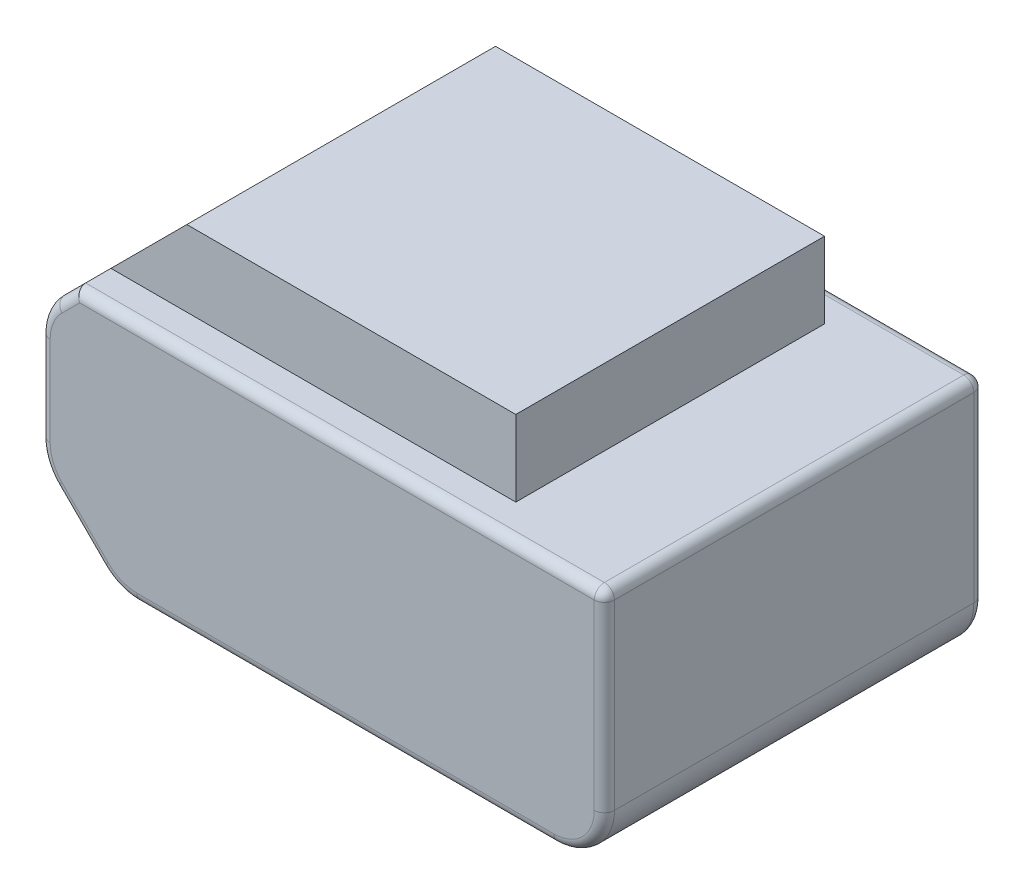
SolidWorks part; units mm, degrees
ref_plane "Front Plane" through (0, 0, 0) normal (0, 0, 1) x (1, 0, 0)
ref_plane "Top Plane" through (0, 0, 0) normal (0, 1, 0) x (1, 0, 0)
ref_plane "Right Plane" through (0, 0, 0) normal (1, 0, 0) x (0, 0, -1)
sketch "Sketch1" plane through (0, 0, 0) normal (0, 1, 0) x (1, 0, 0)
  line L1 (-55.75, 37.5) -> (55.75, 37.5)
  line L2 (-55.75, 37.5) -> (-55.75, -37.5)
  line L3 (-55.75, -37.5) -> (55.75, -37.5)
  line L4 (55.75, 37.5) -> (55.75, -37.5)
  line L5 (-55.75, 37.5) -> (55.75, -37.5) construction
  line L6 (-55.75, -37.5) -> (55.75, 37.5) construction
  point P0 (0, 0)
  dimension "D1" = 75
  dimension "D2" = 111.5
extrude "Boss-Extrude1" add sketch "Sketch1" along normal blind 63
sketch "Sketch2" plane through (0, 0, 37.5) normal (0, 0, 1) x (1, 0, 0)
  line L0 (-55.75, 41) -> (-33.75, 63)
  line L1 (-55.75, 63) -> (-55.75, 0) construction
  line L2 (-55.75, 63) -> (55.75, 63) construction
  line L3 (-55.75, 41) -> (-55.75, 63)
  line L4 (-55.75, 63) -> (-33.75, 63)
  line L5 (-55.75, 15) -> (-40.75, 0)
  line L6 (-55.75, 0) -> (55.75, 0) construction
  line L7 (-55.75, 15) -> (-55.75, 0)
  line L8 (-55.75, 0) -> (-40.75, 0)
  dimension "D1" = 22
  dimension "D2" = 45
  dimension "D3" = 15
  dimension "D4" = 45
extrude "Cut-Extrude1" cut sketch "Sketch2" against normal up to next
sketch "Sketch3" plane through (0, 63, 0) normal (0, 1, 0) x (1, 0, 0)
  line L0 (-55.75, 0) -> (55.75, 0) construction
  line L1 (-55.75, 37.5) -> (-55.75, -37.5) construction
  line L2 (55.75, -37.5) -> (55.75, 37.5) construction
  line L4 (-55.75, -30.5) -> (31.25, -30.5)
  line L5 (-55.75, -30.5) -> (-55.75, 30.5)
  line L6 (-55.75, 30.5) -> (31.25, 30.5)
  line L7 (31.25, -30.5) -> (31.25, 30.5)
  line L8 (-55.75, -30.5) -> (31.25, 30.5) construction
  line L9 (-55.75, 30.5) -> (31.25, -30.5) construction
  line L11 (-55.75, 37.5) -> (55.75, 37.5)
  line L12 (-55.75, 37.5) -> (-55.75, -37.5)
  line L13 (-55.75, -37.5) -> (55.75, -37.5)
  line L14 (55.75, 37.5) -> (55.75, -37.5)
  point P6 (-12.25, 0)
  line M9 (-33.75, 37.5) -> (-33.75, -37.5)
  line M10 (-33.75, -37.5) -> (55.75, -37.5)
  line M11 (55.75, -37.5) -> (55.75, 37.5)
  line M12 (55.75, 37.5) -> (-33.75, 37.5)
  dimension "D1" = 61
  dimension "D2" = 87
extrude "Cut-Extrude2" cut sketch "Sketch3" against normal blind 15 contours L7 L4 L6 M9 M10 M11 M12 | L12 L13 L4 M9 | L11 L12 L6 M9 region at (-44.75, 63, 34) region at (-1.25, 63, 31.6677) region at (-44.75, 63, -34)
sketch "Sketch4" plane through (0, 0, 0) normal (0, 0, 1) x (1, 0, 0)
  line L0 (-53.6287, 43.1213) -> (-38.6997, 58.0503)
  line L1 (-38.6997, 58.0503) -> (-38.6997, 55.2218)
  line L2 (-38.6997, 55.2218) -> (-50.8003, 43.1213)
  line L3 (-50.8003, 43.1213) -> (-53.6287, 43.1213)
  dimension "D3" = 2
extrude "Cut-Extrude3" cut sketch "Sketch4" against normal mid plane 30
fillet "Fillet1" radius 10 4 edges at (-55.75, 41, 0) (-55.75, 15, 0) (-40.75, 0, 0) (55.75, 0, 0)
fillet "Fillet2" radius 2 21 edges at (-54.9888, 15.3153, -37.5) (-48.25, 7.5, -37.5) (-40.4347, 0.7612, -37.5) (4.5711, 0, -37.5) (52.8211, 2.9289, -37.5) (55.75, 29, -37.5) (3.5, 48, -37.5) (-50.7855, 45.9645, -37.5) (-54.9888, 40.6847, -37.5) (-55.75, 28, -37.5) (3.5, 48, 37.5) (55.75, 29, 37.5) (52.8211, 2.9289, 37.5) (4.5711, 0, 37.5) (-40.4347, 0.7612, 37.5) (-48.25, 7.5, 37.5) (-54.9888, 15.3153, 37.5) (-55.75, 28, 37.5) (-54.9888, 40.6847, 37.5) (-50.7855, 45.9645, 37.5) (55.75, 48, 0)
